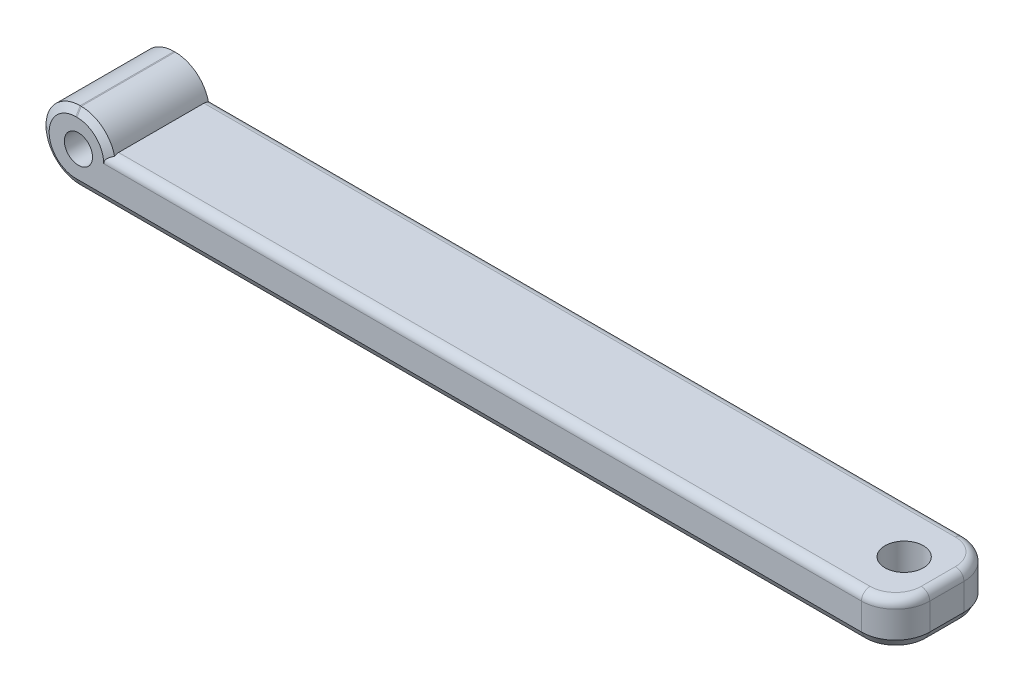
SolidWorks part; units mm, degrees
ref_plane "Front Plane" through (0, 0, 0) normal (0, 0, 1) x (1, 0, 0)
ref_plane "Top Plane" through (0, 0, 0) normal (0, 1, 0) x (1, 0, 0)
ref_plane "Right Plane" through (0, 0, 0) normal (1, 0, 0) x (0, 0, -1)
sketch "Sketch1" plane through (0, 0, 0) normal (0, 1, 0) x (1, 0, 0)
  line L1 (-50, -6) -> (50, -6)
  line L2 (-50, -6) -> (-50, 6)
  line L3 (-50, 6) -> (50, 6)
  line L4 (50, -6) -> (50, 6)
  line L5 (-50, -6) -> (50, 6) construction
  line L6 (-50, 6) -> (50, -6) construction
  point P0 (0, 0)
  dimension "D1" = 100
  dimension "D2" = 12
extrude "Boss-Extrude1" add sketch "Sketch1" along normal blind 5
sketch "Sketch3" plane through (0, 5, 0) normal (0, 1, 0) x (1, 0, 0)
  line L0 (-50, -6) -> (50, -6) construction
  line L1 (-50, 6) -> (-42, 6)
  line L2 (-50, 6) -> (-50, -6)
  line L3 (-50, -6) -> (-42, -6)
  line L4 (-42, 6) -> (-42, -6)
  dimension "D1" = 8
extrude "Boss-Extrude2" add sketch "Sketch3" along normal blind 3
sketch "Sketch4" plane through (0, 0, 6) normal (0, 0, 1) x (1, 0, 0)
  line L0 (-50, 8) -> (-50, 0) construction
  circle A0 centre (-45.7, 4) radius 1.65
  point P4 (-50, 4)
  dimension "D2" = 3.3
  dimension "D1" = 4.3
extrude "Cut-Extrude1" cut sketch "Sketch4" against normal through all
fillet "Fillet1" radius 4 3 edges at (-50, 0, 0) (-50, 8, 0) (-42, 8, 0)
sketch "Sketch5" plane through (0, 5, 0) normal (0, 1, 0) x (1, 0, 0)
  line L0 (-39, 0) -> (-22.2, 0) construction
  line L1 (-39, 1.7) -> (-22.2, 1.7)
  line L2 (-39, -1.7) -> (-22.2, -1.7)
  line L3 (-42, -6) -> (-42, 6) construction
  line L4 (-15.825, 0) -> (0.975, 0) construction
  line L5 (-15.825, 1.7) -> (0.975, 1.7)
  line L6 (-15.825, -1.7) -> (0.975, -1.7)
  line L7 (7.35, 0) -> (24.15, 0) construction
  line L8 (7.35, 1.7) -> (24.15, 1.7)
  line L9 (7.35, -1.7) -> (24.15, -1.7)
  line L10 (30.525, 0) -> (47.325, 0) construction
  line L11 (30.525, 1.7) -> (47.325, 1.7)
  line L12 (30.525, -1.7) -> (47.325, -1.7)
  line L13 (53.7, 0) -> (70.5, 0) construction
  line L14 (53.7, 1.7) -> (70.5, 1.7)
  line L15 (53.7, -1.7) -> (70.5, -1.7)
  arc A0 (-39, 1.7) -> (-39, -1.7) centre (-39, 0) ccw
  arc A1 (-22.2, -1.7) -> (-22.2, 1.7) centre (-22.2, 0) ccw
  arc A2 (-15.825, 1.7) -> (-15.825, -1.7) centre (-15.825, 0) ccw
  arc A3 (0.975, -1.7) -> (0.975, 1.7) centre (0.975, 0) ccw
  arc A4 (7.35, 1.7) -> (7.35, -1.7) centre (7.35, 0) ccw
  arc A5 (24.15, -1.7) -> (24.15, 1.7) centre (24.15, 0) ccw
  arc A6 (30.525, 1.7) -> (30.525, -1.7) centre (30.525, 0) ccw
  arc A7 (47.325, -1.7) -> (47.325, 1.7) centre (47.325, 0) ccw
  arc A8 (53.7, 1.7) -> (53.7, -1.7) centre (53.7, 0) ccw
  arc A9 (70.5, -1.7) -> (70.5, 1.7) centre (70.5, 0) ccw
  point P2 (-30.6, 0)
  point P14 (-7.425, 0)
  point P21 (15.75, 0)
  point P28 (38.925, 0)
  point P33 (62.1, 0)
  dimension "D2" = 1.7
  dimension "D1" = 3
  dimension "D3" = 16.8
  dimension "D4" = 5
extrude "Cut-Extrude2" [suppressed] cut sketch "Sketch5" against normal through all
sketch "Sketch6" plane through (0, 5, 0) normal (0, 1, 0) x (1, 0, 0)
  line L0 (50, -6) -> (50, 6) construction
  circle A0 centre (45, 0) radius 2.25
  point P4 (50, 0)
  dimension "D1" = 4.5
  dimension "D2" = 5
extrude "Cut-Extrude3" cut sketch "Sketch6" against normal through all
fillet "Fillet2" radius 4 2 edges at (50, 2.5, -6) (50, 2.5, 6)
fillet "Fillet3" [suppressed] radius 1
chamfer "Chamfer1" distance 0.5 angle 60 13 edges at (-43.4235, 7.1623, -6) (-45.9365, 8, -6) (-48.8284, 6.8284, -6) (-48.8284, 1.1716, -6) (0, 0, -6) (48.8284, 0, -4.8284) (50, 0, 0) (48.8284, 0, 4.8284) (0, 0, 6) (-48.8284, 1.1716, 6) (-48.8284, 6.8284, 6) (-45.9365, 8, 6) (-43.4235, 7.1623, 6) first distance on face at (-43.68, 6.8311, 0) first distance on face at (-45.9365, 8, 0) first distance on face at (-48.4142, 6.4142, 0) first distance on face at (-48.4142, 1.5858, 0) first distance on face at (45, 0, 2.25)
fillet "Fillet4" radius 1 5 edges at (1.5486, 5, -6) (48.8284, 5, -4.8284) (50, 5, 0) (48.8284, 5, 4.8284) (1.5486, 5, 6)
fillet "Fillet5" [suppressed] radius 1
